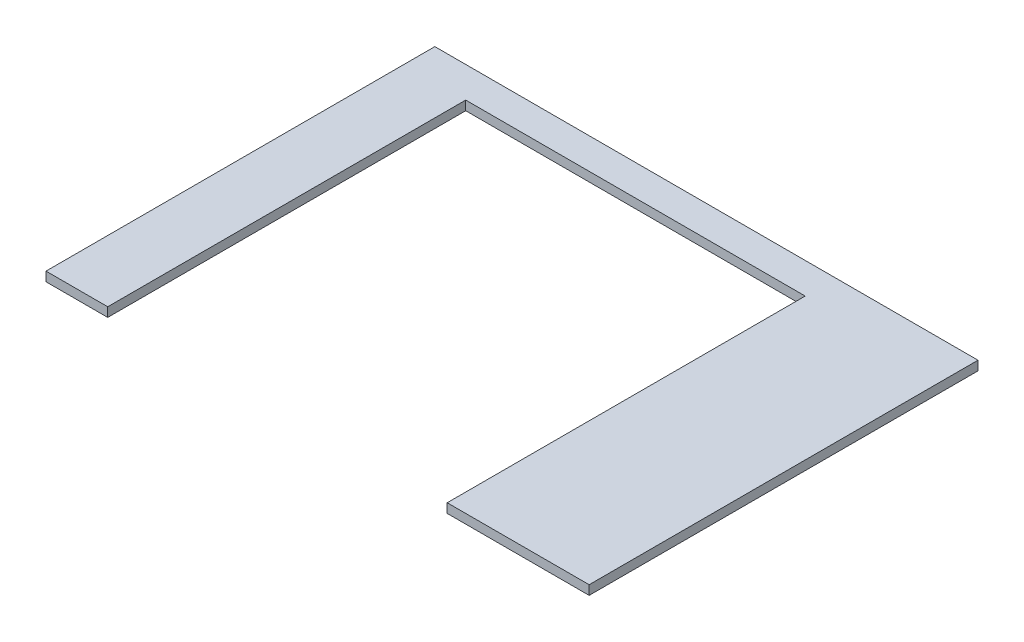
SolidWorks part; units mm, degrees
ref_plane "Спереди" through (0, 0, 0) normal (0, 0, 1) x (1, 0, 0)
ref_plane "Сверху" through (0, 0, 0) normal (0, 1, 0) x (1, 0, 0)
ref_plane "Справа" through (0, 0, 0) normal (1, 0, 0) x (0, 0, -1)
sketch "Эскиз1" plane through (0, 0, 0) normal (0, 1, 0) x (1, 0, 0)
  line L0 (100, 0) -> (100, 580)
  line L1 (100, 0) -> (0, 0)
  line L2 (0, 0) -> (0, 630)
  line L3 (0, 630) -> (880, 630)
  line L4 (880, 0) -> (880, 630)
  line L5 (100, 580) -> (650, 580)
  line L6 (650, 580) -> (650, 0)
  line L7 (650, 0) -> (880, 0)
  dimension "D1" = 100
  dimension "D2" = 880
  dimension "D3" = 50
  dimension "D4" = 230
  dimension "D5" = 630
  dimension "D6" = 630
extrude "Бобышка-Вытянуть1" add sketch "Эскиз1" along normal blind 15
